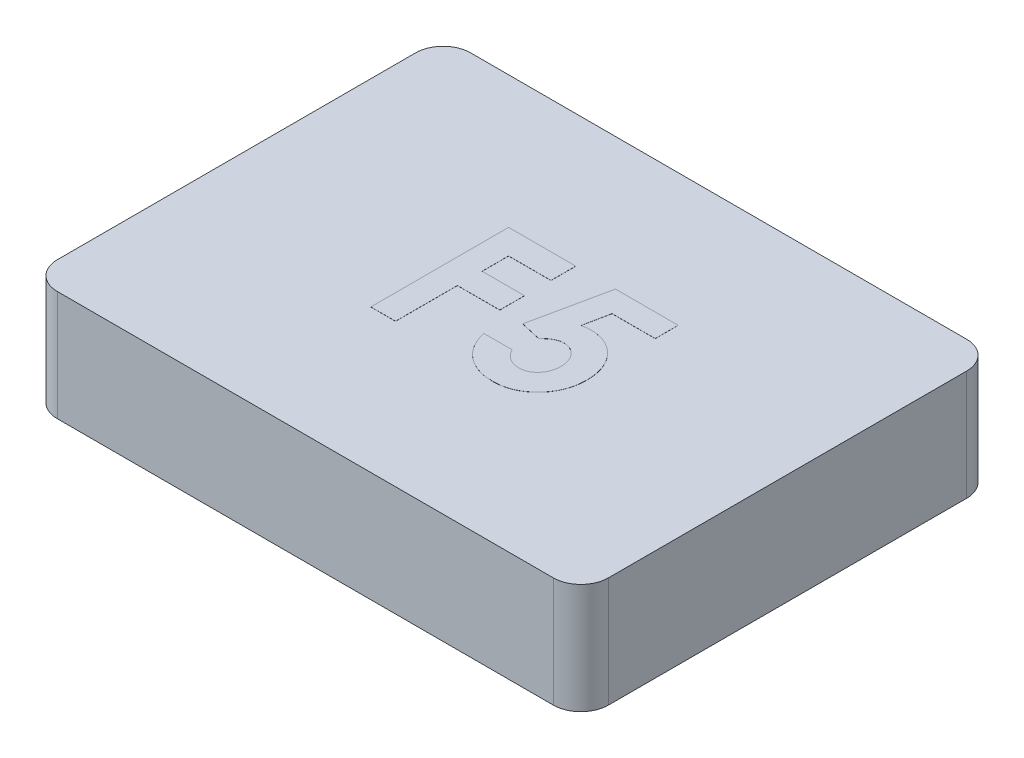
SolidWorks part; units mm, degrees
ref_plane "Front Plane" through (0, 0, 0) normal (0, 0, 1) x (1, 0, 0)
ref_plane "Top Plane" through (0, 0, 0) normal (0, 1, 0) x (1, 0, 0)
ref_plane "Right Plane" through (0, 0, 0) normal (1, 0, 0) x (0, 0, -1)
sketch "Sketch1" plane through (0, 0, 0) normal (0, 1, 0) x (1, 0, 0)
  line L0 (0, 0) -> (12.7, 0)
  line L1 (12.7, 0) -> (12.7, 9.525)
  line L2 (12.7, 9.525) -> (0, 9.525)
  line L3 (0, 9.525) -> (0, 0)
  dimension "D1" = 12.7
  dimension "D2" = 9.525
extrude "Boss-Extrude1" add sketch "Sketch1" along normal blind 2.54
fillet "Fillet1" radius 0.635 4 edges at (0, 1.27, -9.525) (12.7, 1.27, -9.525) (12.7, 1.27, 0) (0, 1.27, 0)
shell "Shell1" thickness 0.635 removed face at (6.35, 0, -4.7625)
sketch "Sketch2" plane through (0, 1.905, 0) normal (0, -1, 0) x (-1, 0, 0)
  line L0 (-0.635, 4.7625) -> (-12.065, 4.7625) construction
  line L1 (-0.635, 8.89) -> (-0.635, 0.635) construction
  line L2 (-12.065, 0.635) -> (-12.065, 8.89) construction
  line L3 (-6.35, 0.635) -> (-6.35, 8.89) construction
  line L4 (-0.635, 0.635) -> (-12.065, 0.635) construction
  line L5 (-12.065, 8.89) -> (-0.635, 8.89) construction
  circle A0 centre (-6.35, 4.7625) radius 2.54
  dimension "D1" = 5.08
extrude "Boss-Extrude2" add sketch "Sketch2" along normal up to surface (1.905 mm away) up to face at (6.35, 0, -4.7625)
sketch "Sketch3" plane through (0, 2.54, 0) normal (0, 1, 0) x (1, 0, 0)
  line L0 (0.635, 0) -> (12.065, 0) construction
  line L1 (0, 8.89) -> (0, 0.635) construction
  text T0 "<b>F5</b>"
  dimension "D1" = 3.302
  dimension "D2" = 4.191
extrude "Boss-Extrude3" add sketch "Sketch3" along normal blind 0.0025
